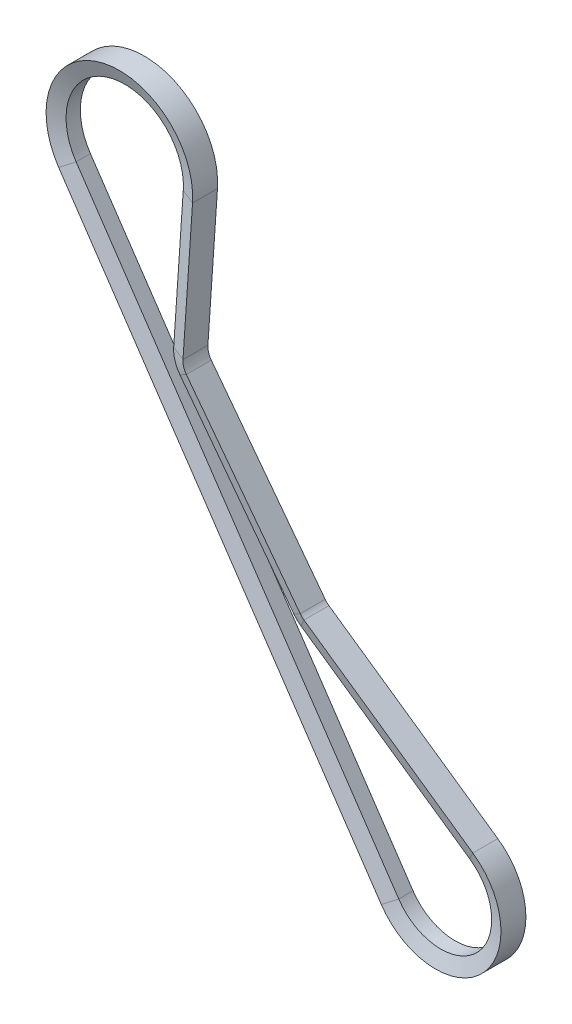
SolidWorks part; units mm, degrees
ref_plane "Front Plane" through (0, 0, 0) normal (0, 0, 1) x (1, 0, 0)
ref_plane "Top Plane" through (0, 0, 0) normal (0, 1, 0) x (1, 0, 0)
ref_plane "Right Plane" through (0, 0, 0) normal (1, 0, 0) x (0, 0, -1)
sketch "Sketch2" plane through (0, 0, 0) normal (0, 0, 1) x (1, 0, 0)
  line L0 (0, 0) -> (1, 0) construction
  line L1 (0, 0) -> (0, 1) construction
  line L9 (-92.8084, 182.002) -> (-96.4621, 128.3604)
  line L10 (-95.1862, 124.0915) -> (-51.6759, 66.7255)
  line L11 (-50.2398, 65.348) -> (14.2647, 20.5309)
  line L12 (-20.7092, -14.0046) -> (-143.938, 168.2197)
  arc A4 (-143.938, 168.2197) -> (-92.8084, 182.002) centre (-120.7436, 183.9048) cw
  arc A5 (-96.4621, 128.3604) -> (-95.1862, 124.0915) centre (-90.1268, 127.9288) ccw
  arc A6 (-51.6759, 66.7255) -> (-50.2398, 65.348) centre (-46.6166, 70.5628) ccw
  arc A7 (14.2647, 20.5309) -> (-20.7092, -14.0046) centre (0, 0) cw
ref_plane "Plane4" through (14.2647, 20.5309, 0) normal (0.8212, -0.5706, 0) x (0, 0, -1)
sketch "Sketch3" plane through (14.2647, 20.5309, 0) normal (0.8212, -0.5706, 0) x (0, 0, -1)
  line L0 (-4.7625, 0) -> (4.7625, 0)
  line L1 (-4.7625, 0) -> (-2.7286, -5.588)
  line L2 (-2.7286, -5.588) -> (2.7286, -5.588)
  line L3 (2.7286, -5.588) -> (4.7625, 0)
  line L4 (0, 0) -> (0, -5.588) construction
  dimension "D1" = 9.525
  dimension "D2" = 5.588
  dimension "D3" = 40
sweep "Sweep1" add profiles "Sketch3" path "Sketch2"
